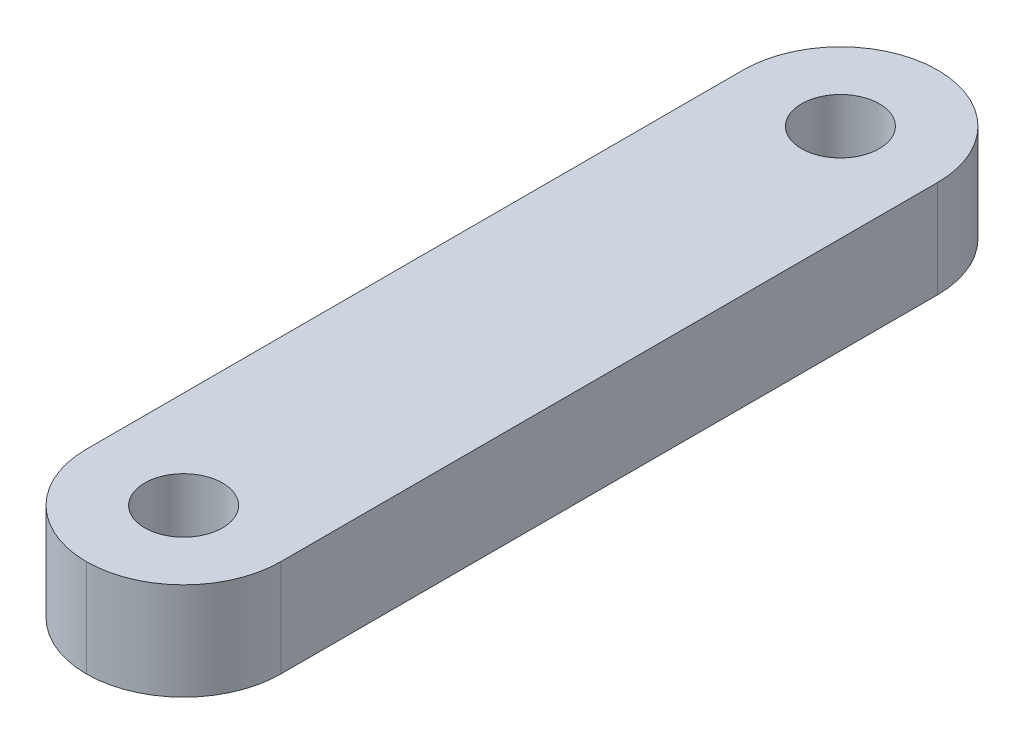
SolidWorks part; units mm, degrees
ref_plane "Front" through (0, 0, 0) normal (0, 0, 1) x (1, 0, 0)
ref_plane "Top" through (0, 0, 0) normal (0, 1, 0) x (1, 0, 0)
ref_plane "Right" through (0, 0, 0) normal (1, 0, 0) x (0, 0, -1)
sketch "Sketch1" plane through (0, 0, 0) normal (0, 0, 1) x (1, 0, 0)
  line L1 (0, 0) -> (8, 0)
  line L2 (0, 0) -> (0, -4)
  line L3 (0, -4) -> (8, -4)
  line L4 (8, 0) -> (8, -4)
  dimension "D1" = 4
  dimension "D2" = 8
extrude "Boss-Extrude1" add sketch "Sketch1" along normal blind 35
sketch "Sketch2" plane through (0, 0, 0) normal (0, 1, 0) x (1, 0, 0)
  line L0 (8, -35) -> (0, -35) construction
  line L1 (8, -35) -> (8, 0) construction
  line L2 (8, 0) -> (0, 0) construction
  circle A0 centre (4, -4) radius 1.6
  circle A1 centre (4, -31) radius 1.6
  dimension "D1" = 3.2
  dimension "D2" = 3.2
  dimension "D3" = 4
  dimension "D4" = 4
  dimension "D5" = 4
  dimension "D6" = 4
extrude "Cut-Extrude1" cut sketch "Sketch2" against normal through all
fillet "Fillet1" radius 4 4 edges at (0, -2, 0) (8, -2, 0) (0, -2, 35) (8, -2, 35)
